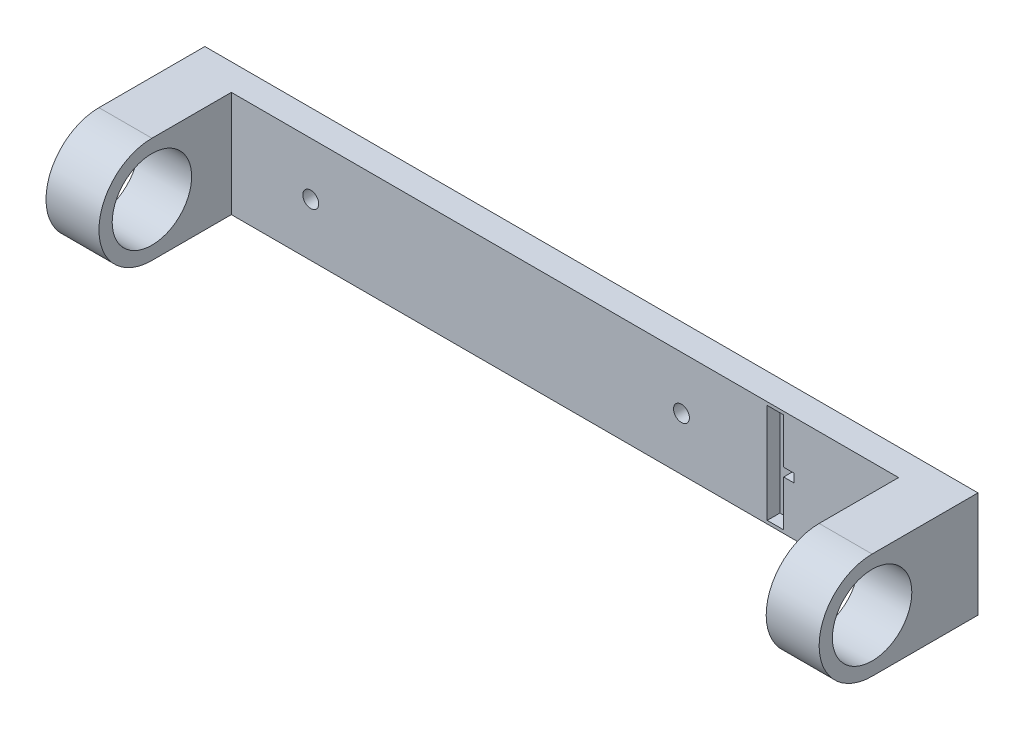
SolidWorks part; units mm, degrees
ref_plane "Plan de face" through (0, 0, 0) normal (0, 0, 1) x (1, 0, 0)
ref_plane "Plan de dessus" through (0, 0, 0) normal (0, 1, 0) x (1, 0, 0)
ref_plane "Plan de droite" through (0, 0, 0) normal (1, 0, 0) x (0, 0, -1)
sketch "Esquisse1" plane through (0, 0, 0) normal (0, 0, 1) x (1, 0, 0)
  line L1 (0, 0) -> (146, 0)
  line L2 (0, 0) -> (0, 20)
  line L3 (0, 20) -> (146, 20)
  line L4 (146, 0) -> (146, 20)
  dimension "D1" = 146
  dimension "D2" = 20
extrude "Boss.-Extru.1" add sketch "Esquisse1" along normal blind 5
sketch "Esquisse2" plane through (0, 0, 5) normal (0, 0, 1) x (1, 0, 0)
  line L0 (146, 20) -> (0, 20) construction
  line L1 (0, 0) -> (10, 0)
  line L2 (0, 0) -> (0, 20)
  line L3 (0, 20) -> (10, 20)
  line L4 (10, 0) -> (10, 20)
  dimension "D1" = 10
extrude "Boss.-Extru.2" add sketch "Esquisse2" along normal blind 30
sketch "Esquisse3" plane through (0, 0, 0) normal (-1, 0, 0) x (0, 0, 1)
  line L0 (0, 20) -> (0, 0) construction
  line L1 (35, 20) -> (0, 20) construction
  line L2 (35, 20) -> (35, 0) construction
  line L3 (35, 0) -> (0, 0) construction
  line L4 (35, 20) -> (20, 20)
  line L5 (35, 20) -> (35, 0)
  line L6 (35, 0) -> (20, 0)
  circle A0 centre (20, 10) radius 7.5
  arc A1 (20, 0) -> (20, 20) centre (20, 10) ccw
  dimension "D2" = 15
  dimension "D4" = 20
  dimension "D1" = 20
  dimension "D3" = 10
extrude "Enlèv. mat.-Extru.1" cut sketch "Esquisse3" against normal up to surface (10 mm away) up to face at (10, 10, 20)
ref_plane "Plan1" through (73, 0, 0) normal (1, 0, 0) x (0, 0, -1)
mirror "Symétrie1" about plane through (73, 0, 0) normal (1, 0, 0) of "Enlèv. mat.-Extru.1", "Boss.-Extru.2"
sketch "Esquisse5" plane through (0, 0, 5) normal (0, 0, 1) x (1, 0, 0)
  line L0 (136, 20) -> (10, 20) construction
  line L1 (111.2, 19.4) -> (114.3, 19.4)
  line L2 (111.2, 19.4) -> (111.2, 0.6)
  line L3 (111.2, 0.6) -> (114.3, 0.6)
  line L4 (114.3, 19.4) -> (114.3, 10.85)
  line L5 (136, 0) -> (136, 20) construction
  line L6 (114.3, 10.85) -> (116.3, 10.85)
  line L7 (116.3, 10.85) -> (116.3, 9.25)
  line L8 (116.3, 9.25) -> (114.3, 9.25)
  line L9 (114.3, 9.25) -> (114.3, 0.6)
  dimension "D1" = 18.8
  dimension "D2" = 3.1
  dimension "D3" = 0.6
  dimension "D4" = 21.7
  dimension "D5" = 8.65
  dimension "D6" = 1.6
  dimension "D7" = 2
extrude "Enlèv. mat.-Extru.2" cut sketch "Esquisse5" against normal offset from surface (2.4 mm away) 2.6 up to face at (73, 10, 0)
sketch "Esquisse6" plane through (0, 0, 5) normal (0, 0, 1) x (1, 0, 0)
  line L0 (136, 20) -> (10, 20) construction
  line L1 (10, 0) -> (10, 20) construction
  circle A0 centre (25, 10) radius 1.5
  circle A1 centre (95, 10) radius 1.5
  dimension "D1" = 3
  dimension "D4" = 3
  dimension "D2" = 10
  dimension "D3" = 15
  dimension "D5" = 10
  dimension "D6" = 70
extrude "Enlèv. mat.-Extru.3" cut sketch "Esquisse6" against normal up to surface (5 mm away) up to face at (73, 10, 0)
equation "\"D3@Esquisse5\"=(20-\"D1@Esquisse5\")/2"
